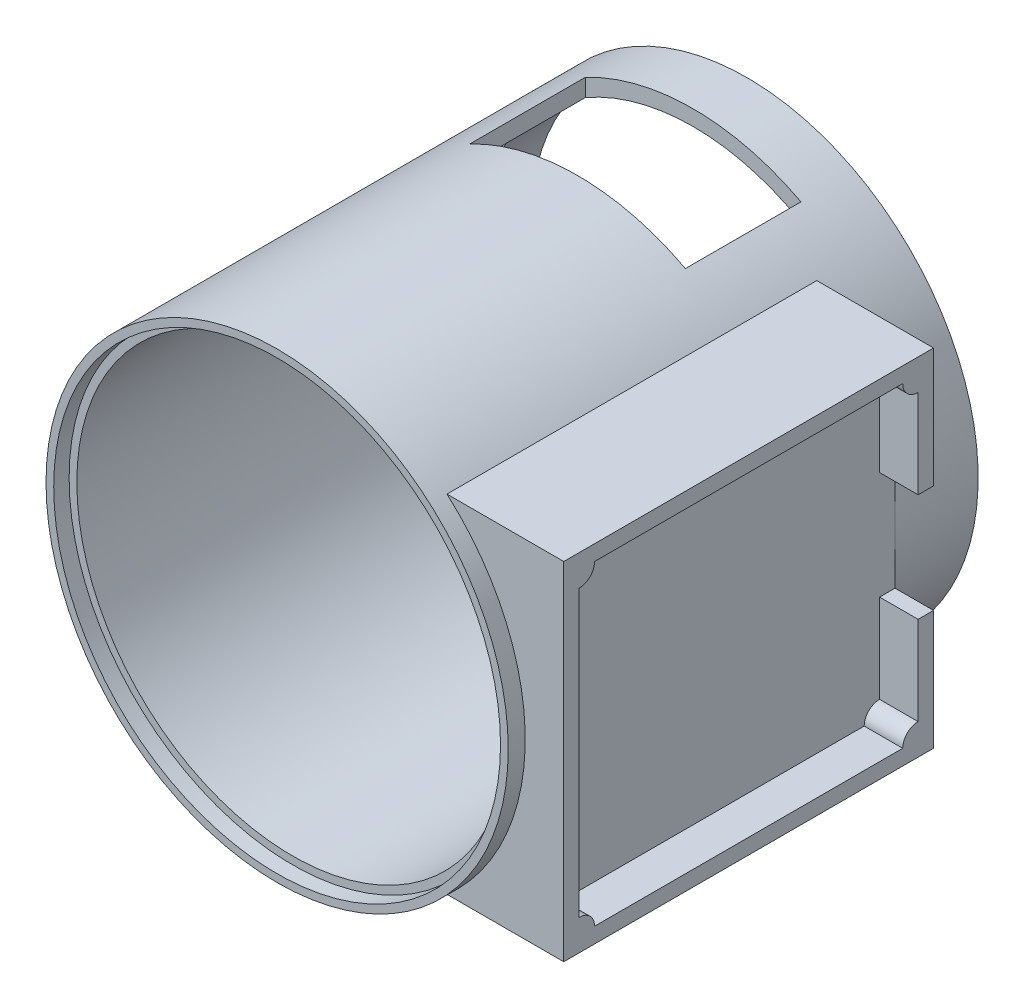
SolidWorks part; units mm, degrees
ref_plane "前视基准面" through (0, 0, 0) normal (0, 0, 1) x (1, 0, 0)
ref_plane "上视基准面" through (0, 0, 0) normal (0, 1, 0) x (1, 0, 0)
ref_plane "右视基准面" through (0, 0, 0) normal (1, 0, 0) x (0, 0, -1)
sketch "草图1" plane through (0, 0, 0) normal (0, 0, 1) x (1, 0, 0)
  circle A0 centre (0, 0) radius 30
  circle A1 centre (0, 0) radius 28
extrude "凸台-拉伸1" add sketch "草图1" along normal blind 2
sketch "草图2" plane through (0, 0, 2) normal (0, 0, 1) x (1, 0, 0)
  circle A0 centre (0, 0) radius 30
  circle A1 centre (0, 0) radius 28
extrude "凸台-拉伸2" add sketch "草图2" along normal blind 52
sketch "草图3" plane through (0, 0, 0) normal (0, 1, 0) x (1, 0, 0)
  line L0 (-10, 0) -> (10, 0)
  line L1 (-10, 0) -> (-10, -20)
  line L2 (-10, -20) -> (10, -20)
  line L3 (10, -20) -> (10, 0)
  line L4 (28, 0) -> (-28, 0) construction
extrude "切除-拉伸1" [suppressed] cut sketch "草图3" against normal through all both and the other way through all
sketch "草图5" plane through (0, 0, 0) normal (0, 1, 0) x (1, 0, 0)
  line L0 (0, 2.5884) -> (0, -39.4963)
pattern_circular "阵列(圆周)1" [suppressed] count 4 over 360 about axis through (0, 0, -2.5884) along (0, 0, 1)
sketch "草图6" plane through (0, 0, 54) normal (0, 0, 1) x (1, 0, 0)
  circle A0 centre (0, 0) radius 28
  circle A1 centre (0, 0) radius 29
extrude "切除-拉伸2" cut sketch "草图6" against normal blind 2
sketch "草图7" plane through (0, 0, 0) normal (0, 0, -1) x (-1, 0, 0)
  circle A0 centre (0, 0) radius 28
  circle A1 centre (0, 0) radius 30
extrude "凸台-拉伸3" add sketch "草图7" along normal blind 7
ref_plane "基准面1" through (30, 0, 0) normal (1, 0, 0) x (0, 0, -1)
sketch "草图8" plane through (30, 0, 0) normal (1, 0, 0) x (0, 0, -1)
  line L0 (-3.7941, 22.5) -> (-3.7941, -22.5)
  line L2 (-3.7941, 22.5) -> (-51.7941, 22.5)
  line L3 (-51.7941, 22.5) -> (-51.7941, -22.5)
  line L4 (-51.7941, -22.5) -> (-3.7941, -22.5)
extrude "凸台-拉伸7" add sketch "草图8" against normal up to surface (10.1569 mm away)
sketch "草图9" plane through (0, 0, 0) normal (0, 1, 0) x (1, 0, 0)
  line L0 (-14, 0) -> (14, 0)
  line L1 (14, 0) -> (14, -15)
  line L2 (14, -15) -> (-14, -15)
  line L3 (-14, -15) -> (-14, 0)
extrude "切除-拉伸3" cut sketch "草图9" against normal through all
pattern_circular "阵列(圆周)2" count 3 every 90 about axis through (0, 0, 0) along (0, 0, 1) of "切除-拉伸3"
sketch "草图10" plane through (30, 0, 0) normal (1, 0, 0) x (0, 0, -1)
  line L0 (-3.7941, 22.5) -> (-3.7941, 7)
  line L2 (-51.7941, 22.5) -> (-51.7941, -22.5)
  line L7 (-51.7941, 22.5) -> (-3.7941, 22.5)
  line L9 (-47.7941, 20.5) -> (-7.7941, 20.5)
  line L10 (-49.7941, 18.5) -> (-49.7941, -18.5)
  line L11 (-47.7941, -20.5) -> (-7.7941, -20.5)
  line L12 (-5.7941, 18.5) -> (-5.7941, 7)
  line L13 (-5.7941, -7) -> (-5.7941, -18.5)
  line L15 (-51.7941, -22.5) -> (-3.7941, -22.5)
  line L16 (-3.7941, -7) -> (-3.7941, -22.5)
  line L17 (-3.7941, 7) -> (-5.7941, 7)
  line L22 (-3.7941, -7) -> (-5.7941, -7)
  arc A5 (-49.7941, 18.5) -> (-47.7941, 20.5) centre (-49.7941, 20.5) ccw
  arc A6 (-47.7941, -20.5) -> (-49.7941, -18.5) centre (-49.7941, -20.5) ccw
  arc A7 (-5.7941, -18.5) -> (-7.7941, -20.5) centre (-5.7941, -20.5) ccw
  arc A9 (-7.7941, 20.5) -> (-5.7941, 18.5) centre (-5.7941, 20.5) ccw
extrude "凸台-拉伸8" add sketch "草图10" along normal blind 5
sketch "草图15" plane through (30, 0, 0) normal (1, 0, 0) x (0, 0, -1)
  line L1 (-51.7941, 22.5) -> (-3.7941, 22.5)
  line L2 (-51.7941, 22.5) -> (-51.7941, -22.5)
  line L3 (-51.7941, -22.5) -> (-3.7941, -22.5)
  line L4 (-3.7941, 22.5) -> (-3.7941, -22.5)
